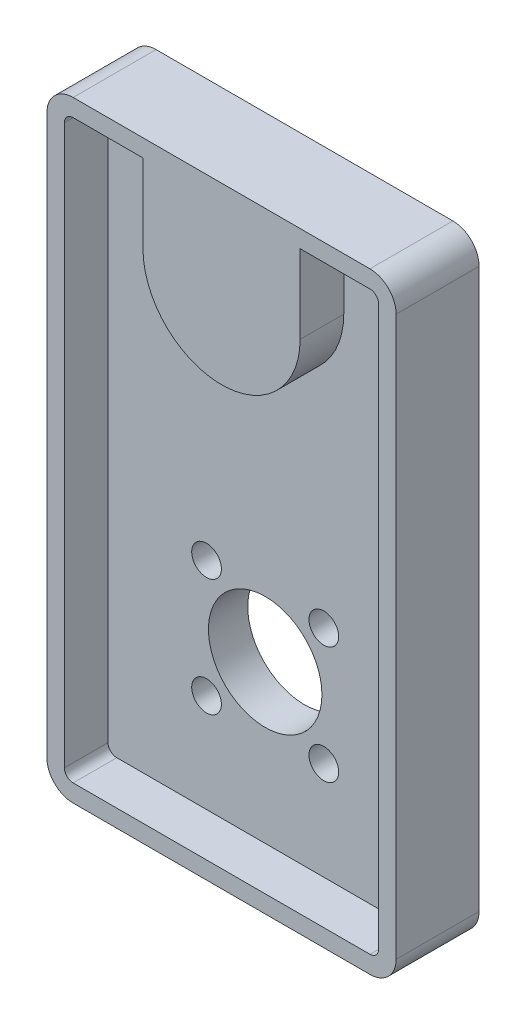
SolidWorks part; units mm, degrees
ref_plane "Front Plane" through (0, 0, 0) normal (0, 0, 1) x (1, 0, 0)
ref_plane "Top Plane" through (0, 0, 0) normal (0, 1, 0) x (1, 0, 0)
ref_plane "Right Plane" through (0, 0, 0) normal (1, 0, 0) x (0, 0, -1)
sketch "Sketch1" plane through (0, 0, 0) normal (0, 0, 1) x (1, 0, 0)
  line L0 (20, 0) -> (20, 70) construction
  line L1 (0, 0) -> (40, 0)
  line L2 (0, 0) -> (0, 70)
  line L3 (0, 70) -> (40, 70)
  line L4 (40, 0) -> (40, 70)
  line L5 (0, 20) -> (40, 20) construction
  line L6 (13.2825, 26.7175) -> (40, 0) construction
  line L7 (26.7175, 26.7175) -> (0, 0) construction
  circle A0 centre (20, 20) radius 9.5 construction
  circle A2 centre (26.7175, 13.2825) radius 1.7
  circle A3 centre (26.7175, 26.7175) radius 1.7
  circle A4 centre (13.2825, 26.7175) radius 1.7
  circle A5 centre (13.2825, 13.2825) radius 1.7
  circle A6 centre (20, 20) radius 6.5
  dimension "D4" = 19
  dimension "D5" = 3.4
  dimension "D6" = 13
  dimension "D1" = 70
  dimension "D2" = 40
  dimension "D3" = 20
extrude "Boss-Extrude1" add sketch "Sketch1" along normal blind 4.5
sketch "Sketch3" plane through (0, 0, 4.5) normal (0, 0, 1) x (1, 0, 0)
  line L0 (0, 0) -> (40, 0) construction
  line L1 (40, 0) -> (40, 70) construction
  line L2 (40, 70) -> (0, 70) construction
  line L3 (0, 70) -> (0, 0) construction
  line L4 (0, 0) -> (40, 0)
  line L5 (40, 0) -> (40, 70)
  line L6 (40, 70) -> (0, 70)
  line L7 (0, 70) -> (0, 0)
  line L8 (2, 2) -> (38, 2)
  line L9 (38, 2) -> (38, 68)
  line L10 (38, 68) -> (29, 68)
  line L11 (2, 68) -> (2, 2)
  line L12 (20, 68) -> (20, 2) construction
  line L13 (2, 59) -> (38, 59) construction
  line L14 (11, 59) -> (11, 68)
  line L15 (29, 59) -> (29, 68)
  line L16 (11, 68) -> (2, 68)
  line L17 (38, 68) -> (2, 68) construction
  circle A0 centre (20, 59) radius 7 construction
  arc A1 (11, 59) -> (29, 59) centre (20, 59) ccw
  circle A2 centre (20, 59) radius 9 construction
  dimension "D3" = 14
  dimension "D2" = 11
  dimension "D1" = 2
  dimension "D4" = 2
extrude "Boss-Extrude2" add sketch "Sketch3" along normal blind 5
sketch "Sketch4" plane through (0, 0, 0) normal (0, 0, -1) x (-1, 0, 0)
  line L0 (-20, 70) -> (-20, 0) construction
  line L1 (-40, 70) -> (0, 70) construction
  line L2 (0, 0) -> (-40, 0) construction
  line L3 (-40, 66) -> (0, 66) construction
  line L4 (-40, 0) -> (-40, 70) construction
  line L5 (0, 70) -> (0, 0) construction
  line L6 (-40, 59) -> (0, 59) construction
  circle A0 centre (-20, 59) radius 7
  dimension "D3" = 14
  dimension "D1" = 4
  dimension "D2" = 7
extrude "Cut-Extrude1" cut sketch "Sketch4" against normal offset from surface (7.5 mm away) 2 up to face at (20, 35, 9.5)
fillet "Fillet1" radius 3 4 edges at (0, 70, 4.75) (40, 70, 4.75) (40, 0, 4.75) (0, 0, 4.75)
fillet "Fillet2" radius 1 4 edges at (38, 68, 7) (2, 68, 7) (38, 2, 7) (2, 2, 7)
